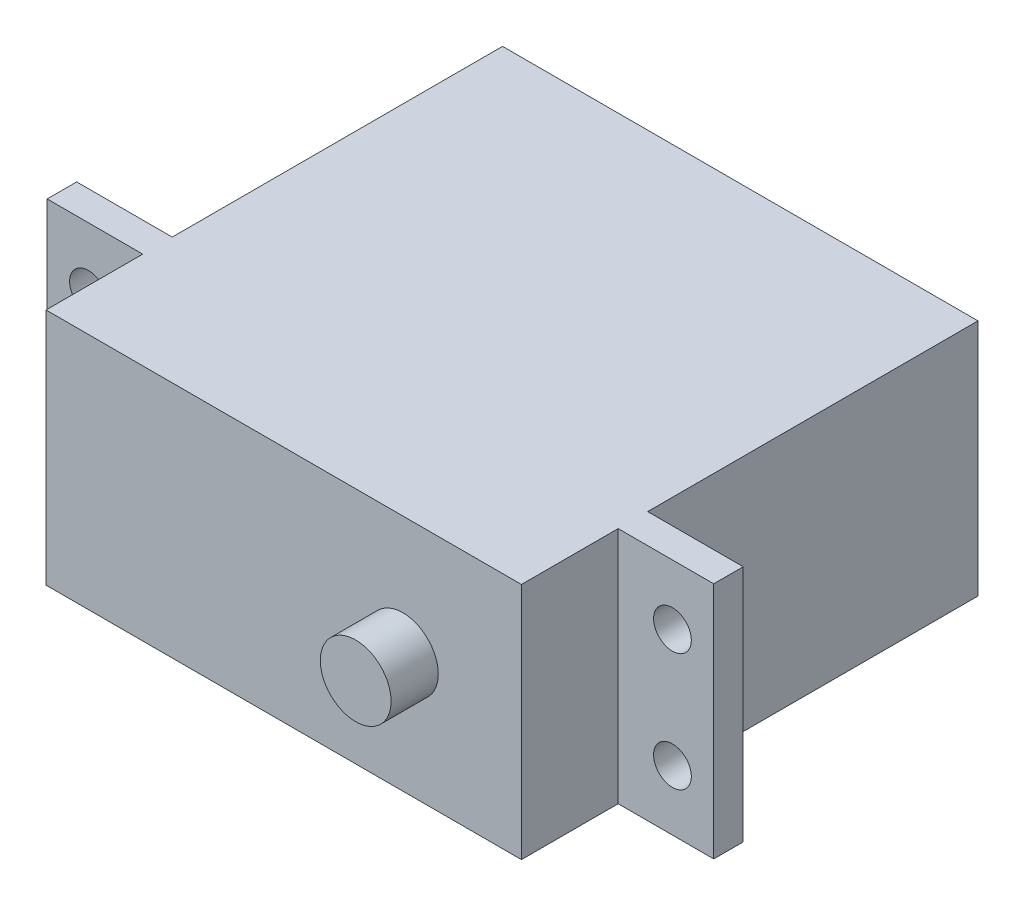
SolidWorks part; units mm, degrees
ref_plane "Front Plane" through (0, 0, 0) normal (0, 0, 1) x (1, 0, 0)
ref_plane "Top Plane" through (0, 0, 0) normal (0, 1, 0) x (1, 0, 0)
ref_plane "Right Plane" through (0, 0, 0) normal (1, 0, 0) x (0, 0, -1)
ref_plane "Case Bottom" through (0, 0, -26) normal (0, 0, 1) x (1, 0, 0)
ref_plane "Tab Bottom" through (0, 0, 2) normal (0, 0, 1) x (1, 0, 0)
ref_plane "Case Top" through (0, 0, 12.7) normal (0, 0, 1) x (1, 0, 0)
sketch "Case Sketch" plane through (0, 0, -26) normal (0, 0, 1) x (1, 0, 0)
  line L0 (-121.25, 73.3) -> (-80.95, 73.3)
  line L1 (-80.95, 73.3) -> (-80.95, 93.5)
  line L2 (-80.95, 93.5) -> (-121.25, 93.5)
  line L3 (-121.25, 93.5) -> (-121.25, 73.3)
extrude "Case" add sketch "Case Sketch" along normal blind 38.7
sketch "Tabs Sketch" plane through (0, 0, 2) normal (0, 0, 1) x (1, 0, 0)
  line L0 (-129.35, 73.3) -> (-72.85, 73.3)
  line L1 (-72.85, 73.3) -> (-72.85, 93.5)
  line L2 (-72.85, 93.5) -> (-129.35, 93.5)
  line L3 (-129.35, 93.5) -> (-129.35, 73.3)
extrude "Tabs" add sketch "Tabs Sketch" along normal blind 2.5
sketch "Shaft Sketch" plane through (0, 0, 12.7) normal (0, 0, 1) x (1, 0, 0)
  circle A0 centre (-91, 83.4) radius 3
extrude "Shaft" add sketch "Shaft Sketch" along normal blind 4
sketch "Tab Holes Sketch" plane through (0, 0, 2) normal (0, 0, 1) x (1, 0, 0)
  circle A0 centre (-125.85, 78.4) radius 1.6
  circle A1 centre (-125.85, 88.4) radius 1.6
  circle A2 centre (-76.35, 78.4) radius 1.6
  circle A3 centre (-76.35, 88.4) radius 1.6
extrude "Tab Holes" cut sketch "Tab Holes Sketch" along normal blind 2.5
ref_plane "Shaft Plane X" through (-91, 0, 0) normal (1, 0, 0) x (0, 0, -1)
ref_plane "Shaft Plane Y" through (0, 83.4, 0) normal (0, 1, 0) x (1, 0, 0)
ref_axis "Shaft Axis" through (-91, 83.4, 18.835) along (0, 0, -1)
